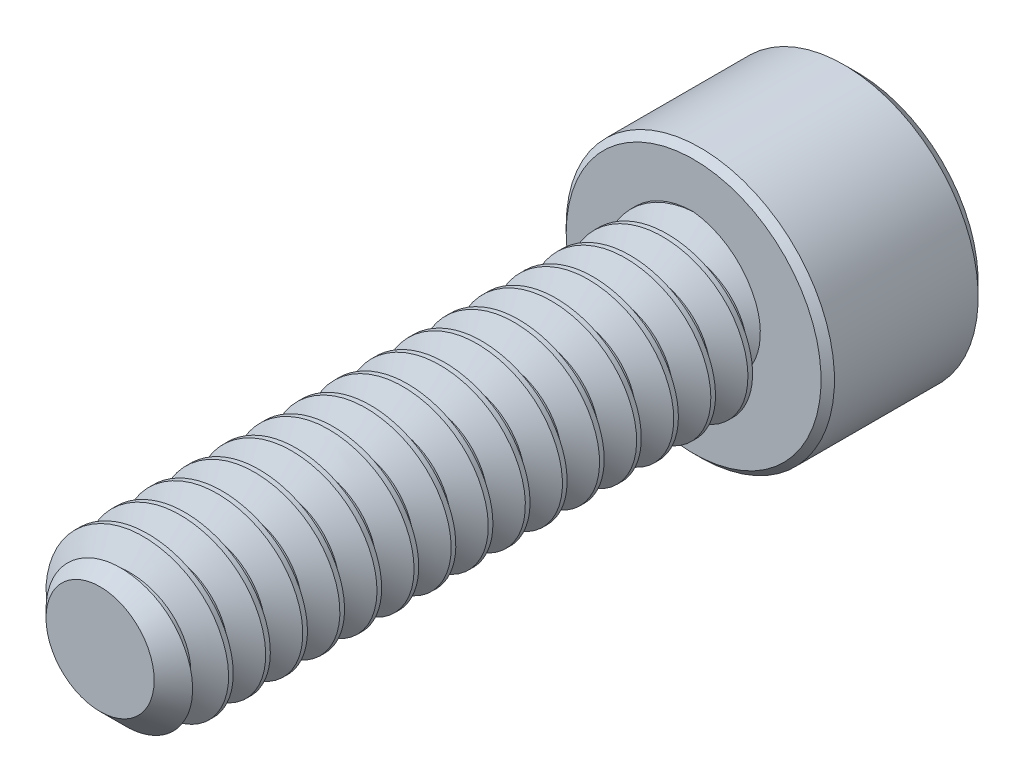
SolidWorks part; units mm, degrees
ref_plane "Front Plane" through (0, 0, 0) normal (0, 0, 1) x (1, 0, 0)
ref_plane "Top Plane" through (0, 0, 0) normal (0, 1, 0) x (1, 0, 0)
ref_plane "Right Plane" through (0, 0, 0) normal (1, 0, 0) x (0, 0, -1)
sketch "Sketch0" plane through (0, 0, 0) normal (1, 0, 0) x (0, 0, -1)
  line L0 (0, 0) -> (12.7, 0) construction
  point P2 (16.2052, 0)
  point P4 (0, 0)
  dimension "D1" = 12.7
  dimension "D2" = 3.5052
  dimension "Min Thread" = 0
sketch "Sketch1" plane through (0, 0, 0) normal (0, 0, 1) x (1, 0, 0)
  circle A0 centre (0, 0) radius 1.7526
  dimension "OD" = 3.5052
extrude "Extrude1" add sketch "Sketch1" against normal blind 12.7
sketch "Sketch2" plane through (0, 0, 0) normal (0, 0, 1) x (1, 0, 0)
  circle A0 centre (0, 0) radius 1.7526 construction
  circle A1 centre (0, 0) radius 1.7526
curve "Helix/Spiral1" pitch 0.7937 height 13.4937 turns 17 parameters "pitch"=0.7937
chamfer "Chamfer3" distance 0.5953 angle 45 1 edges at (1.7526, 0, 0)
sketch "Sketch3" plane through (0, 0, 0) normal (1, 0, 0) x (0, 0, -1)
  line L0 (-0.6945, 1.7526) -> (-0.3969, 1.237)
  line L1 (-0.3969, 1.237) -> (-0.2977, 1.237)
  line L2 (-0.2977, 1.237) -> (0, 1.7526)
  line L3 (-0.6945, 1.7526) -> (0, 1.7526)
  line L4 (-0.3473, 1.7526) -> (-0.3473, 1.237) construction
  line L5 (-0.5457, 1.4948) -> (-0.1488, 1.4948) construction
  line L6 (0, 1.7526) -> (0, -1.7526) construction
  dimension "D1" = 0.0992
  dimension "D2" = 0.3969
  dimension "D3" = 60
sweep "Cut-Sweep1" cut profiles "Sketch3" path "Helix/Spiral1"
sketch "Sketch5" plane through (0, 0, 0) normal (1, 0, 0) x (0, 0, -1)
  line L0 (12.7, -1.2539) -> (12.7, 1.2505) construction
  line L1 (12.7, 1.7526) -> (0, 1.7526)
  line L2 (12.7, 1.7526) -> (12.7, 0)
  line L3 (12.7, 0) -> (-0.6379, 0)
  line L4 (0, 0) -> (12.7, 0) construction
  line L5 (0, 1.7526) -> (-0.6379, 0)
  line L6 (0, 0) -> (15.24, 0) construction
  dimension "D1" = 70
  dimension "D3" = 2.54
revolve "partially thread" [suppressed] add sketch "Sketch5" angle 360 about L6
sketch "Sketch6" plane through (0, 0, -12.7) normal (0, 0, -1) x (-1, 0, 0)
  circle A0 centre (0, 0) radius 2.8702
  dimension "head dia" = 5.7404
extrude "Extrude2" add sketch "Sketch6" along normal blind 3.5052
sketch "Sketch7" plane through (0, 0, -16.2052) normal (0, 0, -1) x (-1, 0, 0)
  line L1 (0, 1.604) -> (-1.3891, 0.802)
  line L2 (-1.3891, 0.802) -> (-1.3891, -0.802)
  line L3 (-1.3891, -0.802) -> (0, -1.604)
  line L4 (0, -1.604) -> (1.3891, -0.802)
  line L5 (1.3891, -0.802) -> (1.3891, 0.802)
  line L6 (1.3891, 0.802) -> (0, 1.604)
  circle A0 centre (0, 0) radius 1.3891 construction
  dimension "hex dia" = 2.7781
extrude "Cut-Extrude1" cut sketch "Sketch7" against normal blind 2.0836
sketch "Sketch8" plane through (0, 0, -16.2052) normal (0, 0, -1) x (-1, 0, 0)
  circle A0 centre (0, 0) radius 1.604
extrude "Cut-Extrude2" cut sketch "Sketch8" against normal through all draft 45
chamfer "Chamfer1" distance 0.287 angle 45 1 edges at (-2.8702, 0, -16.2052)
chamfer "Chamfer2" distance 0.1435 angle 45 1 edges at (-2.8702, 0, -12.7)
sketch "Sketch9" plane through (0, 0, 0) normal (1, 0, 0) x (0, 0, -1)
  line L0 (0, 1.7526) -> (0, -1.7526) construction
  line L1 (1.9844, 1.7526) -> (1.9844, -1.7526) construction
  line L2 (16.2052, 2.8702) -> (16.2052, -2.8702) construction
  line L3 (12.7, 2.8702) -> (12.7, -2.8702) construction
  line L4 (12.7, 2.7267) -> (12.7, -2.7267) construction
  line L5 (16.2052, -2.5832) -> (16.2052, 2.5832) construction
  line L6 (12.7, -2.8702) -> (12.7, 2.8702) construction
  line L7 (0, 1.1573) -> (0, -1.1573) construction
  line L8 (-0.6945, 1.7526) -> (0, 1.7526) construction
  line L9 (1.9844, 0) -> (0, 0) construction
  dimension "D1" = 1.9844
equation "\"D3@Helix/Spiral1\" = \"screw length@Extrude1\"+\"pitch@Helix/Spiral1\""
equation "\"D1@Sketch3\" = \"pitch@Helix/Spiral1\"*.125"
equation "\"D2@Sketch3\" = \"pitch@Helix/Spiral1\"*.5"
equation "\"D1@Cut-Extrude1\" = \"hex dia@Sketch7\"*.75"
equation "\"D1@Chamfer1\" = \"head dia@Sketch6\"*.05"
equation "\"D1@Sketch9\" = \"pitch@Helix/Spiral1\"*2.50"
equation "\"D1@Chamfer2\" = \"D1@Chamfer1\"/2"
equation "\"D1@Chamfer3\" = \"pitch@Helix/Spiral1\"*.750"
equation "\"D1@Sketch0\" = \"screw length@Extrude1\""
equation "\"D2@Sketch0\" = \"head depth@Extrude2\""
